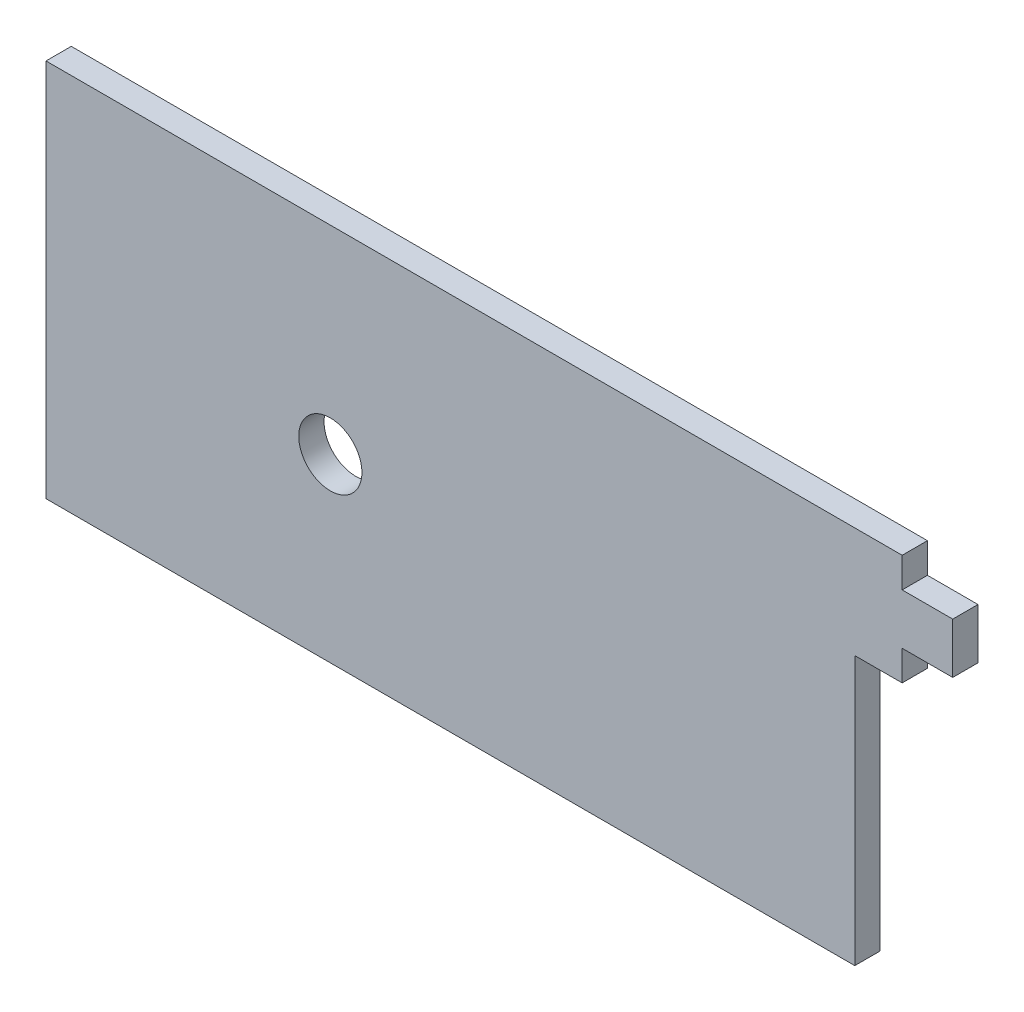
SolidWorks part; units mm, degrees
ref_plane "Front Plane" through (0, 0, 0) normal (0, 0, 1) x (1, 0, 0)
ref_plane "Top Plane" through (0, 0, 0) normal (0, 1, 0) x (1, 0, 0)
ref_plane "Right Plane" through (0, 0, 0) normal (1, 0, 0) x (0, 0, -1)
sketch "Sketch1" plane through (0, 0, 0) normal (0, 0, 1) x (1, 0, 0)
  line L0 (47, 31.4259) -> (54.5, 31.4259)
  line L1 (-81, -28.5741) -> (47, -28.5741)
  line L2 (-81, -28.5741) -> (-81, 31.4259)
  line L3 (-81, 31.4259) -> (47, 31.4259)
  line L4 (47, -28.5741) -> (47, 31.4259) construction
  line L6 (54.5, 13.9259) -> (47, 13.9259)
  line L11 (54.5, 31.4259) -> (54.5, 13.9259) construction
  line L12 (54.5, 31.4259) -> (54.5, 26.6759)
  line L13 (47, 13.9259) -> (47, -28.5741)
  line L14 (54.5, 26.6759) -> (62.5, 26.6759)
  line L15 (62.5, 26.6759) -> (62.5, 18.6759)
  line L16 (62.5, 18.6759) -> (54.5, 18.6759)
  line L17 (54.5, 18.6759) -> (54.5, 13.9259)
  circle A4 centre (-36, 0) radius 5
  dimension "D3" = 17.5
  dimension "D4" = 7.5
  dimension "D5" = 10
  dimension "D1" = 128
  dimension "D6" = 45
  dimension "D2" = 60
  dimension "D7" = 8
  dimension "D8" = 8
extrude "Boss-Extrude1" add sketch "Sketch1" along normal blind 4
